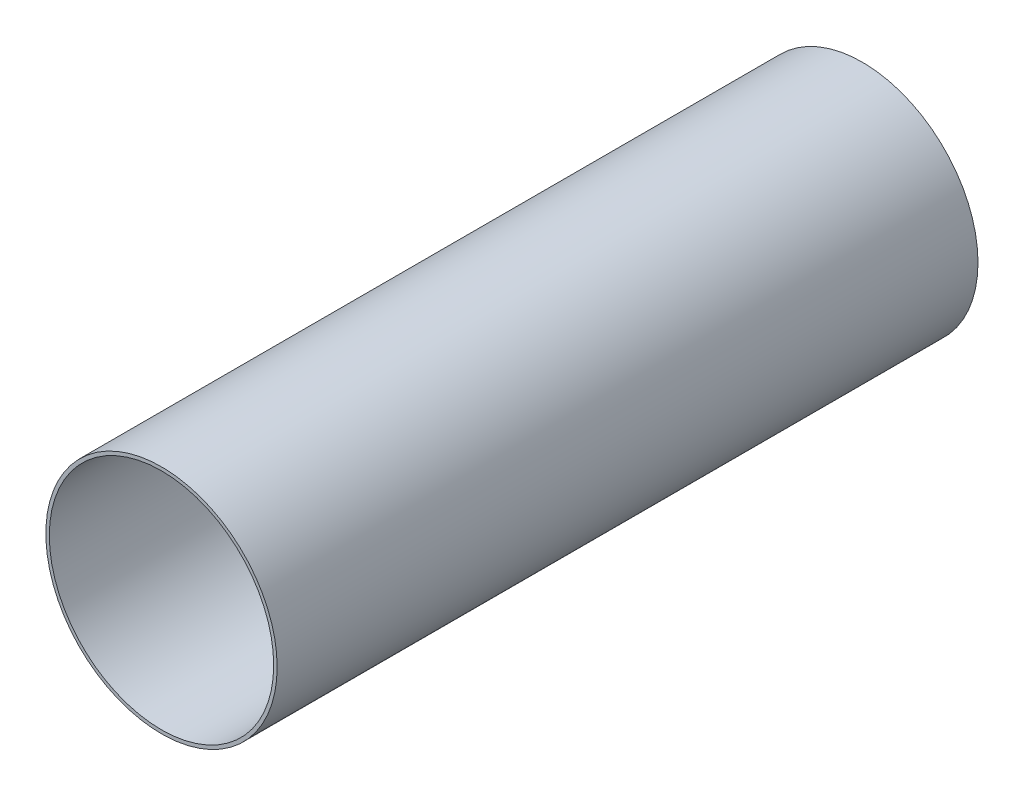
SolidWorks part; units mm, degrees
ref_plane "Front Plane" through (0, 0, 0) normal (0, 0, 1) x (1, 0, 0)
ref_plane "Top Plane" through (0, 0, 0) normal (0, 1, 0) x (1, 0, 0)
ref_plane "Right Plane" through (0, 0, 0) normal (1, 0, 0) x (0, 0, -1)
sketch "Sketch1" plane through (0, 0, 0) normal (0, 0, 1) x (1, 0, 0)
  circle A0 centre (0, 0) radius 50
  circle A1 centre (0, 0) radius 48.5
  dimension "D1" = 100
  dimension "D2" = 97
extrude "Boss-Extrude1" add sketch "Sketch1" along normal blind 303
extrude "Boss-Extrude2" add sketch "Sketch1<2>" along normal blind 3 contours A1 region at (0, 0, 0)
sketch "Sketch1<2>" plane through (0, 0, 0) normal (0, 0, 1) x (1, 0, 0) same geometry as "Sketch1"
